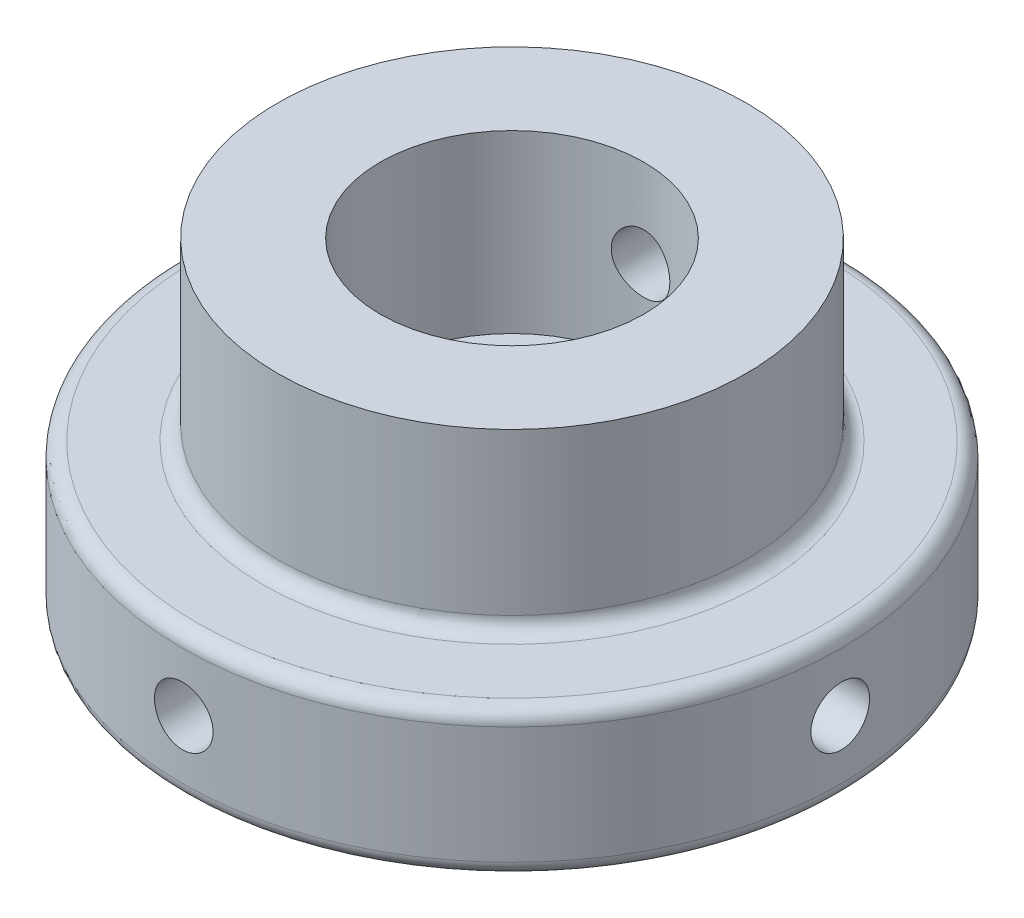
SolidWorks part; units mm, degrees
ref_plane "Front Plane" through (0, 0, 0) normal (0, 0, 1) x (1, 0, 0)
ref_plane "Top Plane" through (0, 0, 0) normal (0, 1, 0) x (1, 0, 0)
ref_plane "Right Plane" through (0, 0, 0) normal (1, 0, 0) x (0, 0, -1)
sketch "Sketch1" plane through (0, 0, 0) normal (0, 1, 0) x (1, 0, 0)
  circle A0 centre (0, 0) radius 45
  circle A1 centre (0, 0) radius 32
  dimension "D1" = 90
  dimension "D2" = 64
extrude "Boss-Extrude1" add sketch "Sketch1" along normal blind 24 contours A1 region at (0, 0, 0)
extrude "Boss-Extrude2" add sketch "Sketch1<4>" against normal blind 20 contours A0 A1 | A1 region at (-43.7272, 0, 0) region at (0, 0, 0)
sketch "Sketch1<4>" plane through (0, 0, 0) normal (0, 1, 0) x (1, 0, 0) same geometry as "Sketch1"
sketch "Sketch2" plane through (0, 24, 0) normal (0, 1, 0) x (1, 0, 0)
  circle A0 centre (0, 0) radius 18
  dimension "D1" = 36
extrude "Cut-Extrude1" cut sketch "Sketch2" against normal up to surface (24 mm away) contours A0 up to face at (0, 0, 32)
sketch "Sketch3" plane through (0, 0, 0) normal (0, 0, 1) x (1, 0, 0)
  line L0 (-45, -10) -> (0, -10) construction
  line L1 (-45, 0) -> (-45, -20) construction
  circle A0 centre (0, -10) radius 4
  dimension "D1" = 8
extrude "Cut-Extrude2" cut sketch "Sketch3" against normal through all from offset 14 contours A0 | A0 region at (0, -10, 0) offset against normal yes
pattern_circular "CirPattern1" count 4 over 360 about axis through (0, -20, 0) along (0, 1, 0) of "Cut-Extrude2"
sketch "Sketch4" plane through (0, 0, 0) normal (0, 0, 1) x (1, 0, 0)
  line L0 (18, 24) -> (-18, 24) construction
  line L1 (0, 12) -> (31.2471, 12) construction
  line L4 (0, 24) -> (0, 0) construction
  circle A0 centre (0, 12) radius 4
  point P4 (0.7529, 12)
  point P6 (0, 0)
  dimension "D2" = 8
  dimension "D1" = 12
extrude "Cut-Extrude3" cut sketch "Sketch4" against normal through all
fillet "Fillet1" radius 2 3 edges at (0, 0, 32) (0, 0, 45) (0, -20, 45)
